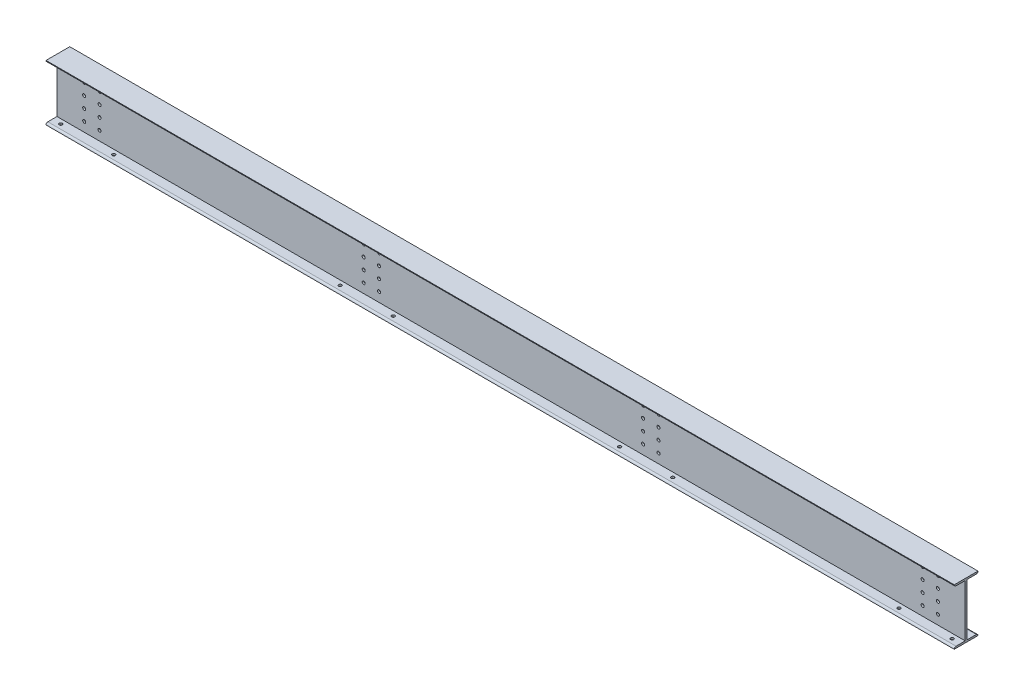
SolidWorks part; units mm, degrees
ref_plane "前视基准面" through (0, 0, 0) normal (0, 0, 1) x (1, 0, 0)
ref_plane "上视基准面" through (0, 0, 0) normal (0, 1, 0) x (1, 0, 0)
ref_plane "右视基准面" through (0, 0, 0) normal (1, 0, 0) x (0, 0, -1)
sketch "草图1" plane through (0, 0, 0) normal (0, 0, 1) x (1, 0, 0)
  line L1 (0, 400) -> (6500, 400)
  line L2 (0, 400) -> (0, 0)
  line L3 (0, 0) -> (6500, 0)
  line L4 (6500, 400) -> (6500, 0)
  dimension "D1" = 6500
  dimension "D2" = 400
extrude "拉伸1" add sketch "草图1" along normal blind 170
sketch "草图2" plane through (0, 0, 170) normal (0, 0, 1) x (1, 0, 0)
  line L0 (0, 400) -> (0, 0) construction
  line L1 (0, 0) -> (6500, 0) construction
  circle A0 centre (195, 80) radius 11
  dimension "D1" = 195
  dimension "D2" = 80
extrude "切除-拉伸1" cut sketch "草图2" against normal through all
pattern_linear "阵列(线性)1" count 4 spacing 80 along (0, 1, 0) of "切除-拉伸1"
pattern_linear "阵列(线性)2" count 2 spacing 110 along (1, 0, 0) of "切除-拉伸1", "阵列(线性)1"
pattern_linear "阵列(线性)3" count 4 spacing 2000 along (1, 0, 0) of "切除-拉伸1", "阵列(线性)1", "阵列(线性)2"
sketch "草图3" plane through (0, 0, 0) normal (0, -1, 0) x (1, 0, 0)
  line L1 (0, 170) -> (0, 0) construction
  circle A0 centre (60, 45) radius 11
  point P2 (0, 85)
  dimension "D1" = 40
  dimension "D2" = 60
extrude "切除-拉伸2" cut sketch "草图3" against normal blind 200
pattern_linear "阵列(线性)4" count 2 spacing 80 along (0, 0, 1) of "切除-拉伸2"
pattern_linear "阵列(线性)5" count 2 spacing 380 along (1, 0, 0) of "切除-拉伸2", "阵列(线性)4"
pattern_linear "阵列(线性)6" count 4 spacing 2000 along (1, 0, 0) of "切除-拉伸2", "阵列(线性)4", "阵列(线性)5"
sketch "草图5" plane through (0, 0, 0) normal (-1, 0, 0) x (0, 0, 1)
  line L0 (170, 400) -> (0, 400) construction
  line L1 (170, 0) -> (0, 0) construction
  line L2 (0, 400) -> (0, 0) construction
  line L3 (0, 387) -> (78.5, 387)
  line L4 (0, 387) -> (0, 13)
  line L5 (0, 13) -> (78.5, 13)
  line L6 (78.5, 387) -> (78.5, 13)
  line L7 (170, 400) -> (170, 0) construction
  line L8 (91.5, 387) -> (170, 387)
  line L9 (91.5, 387) -> (91.5, 13)
  line L10 (91.5, 13) -> (170, 13)
  line L11 (170, 387) -> (170, 13)
  line L12 (170, 400) -> (0, 400) construction
  point P17 (85, 400)
  dimension "D1" = 13
  dimension "D2" = 13
  dimension "D3" = 6.5
extrude "切除-拉伸3" cut sketch "草图5" against normal through all
fillet "圆角1" radius 13 1 edges at (3250, 13, 170)
fillet "圆角2" radius 13 1 edges at (3250, 387, 170)
fillet "圆角3" radius 13 1 edges at (3250, 13, 0)
fillet "圆角4" radius 13 1 edges at (3250, 387, 0)
